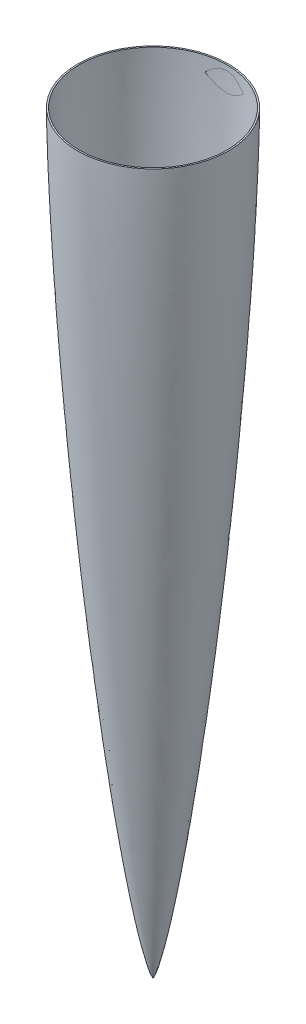
SolidWorks part; units mm, degrees
ref_plane "Front Plane" through (0, 0, 0) normal (1, 0, 0) x (0, 1, 0)
ref_plane "Top Plane" through (0, 0, 0) normal (0, 0, 1) x (0, 1, 0)
ref_plane "Right Plane" through (0, 0, 0) normal (0, 1, 0) x (-1, 0, 0)
sketch "Sketch2" plane through (0, 0, 0) normal (1, 0, 0) x (0, 1, 0)
  line L0 (0, 0) -> (1524, 0)
  line L1 (1524, 0) -> (1524, 152.4)
  spline S0 degree 4 poles (0, 0) (0.0024, 0.0076) (0.008, 0.0224) (0.0228, 0.0502) (0.0602, 0.1013) (0.1177, 0.1662) (0.1973, 0.2429) (0.3166, 0.346) (0.4663, 0.4619) (0.6411, 0.5854) (0.8409, 0.7163) (1.0863, 0.8681) (1.3805, 1.0392) (1.7988, 1.268) (2.2428, 1.4943) (2.73, 1.7308) (3.3252, 2.0064) (3.9582, 2.287) (5.2484, 2.832) (7.7002, 3.7871) (12.4184, 5.4349) (21.4879, 8.2045) (34.2024, 11.5666) (49.9837, 15.3041) (77.2138, 21.1912) (111.5094, 27.7893) (153.1274, 35.0456) (202.0796, 42.8366) (248.6768, 49.7602) (306.9942, 57.9227) (377.0645, 67.0588) (458.9113, 76.9376) (552.5524, 87.3436) (646.2759, 96.9776) (740.0687, 105.9093) (833.9221, 114.1801) (927.8297, 121.8101) (1021.7871, 128.8013) (1115.791, 135.1367) (1198.0833, 140.0715) (1268.6466, 143.8211) (1327.4672, 146.5841) (1374.5344, 148.5535) (1414.7685, 150.0006) (1448.1647, 151.0109) (1474.7196, 151.6715) (1491.9662, 152.0244) (1506.7504, 152.259) (1516.6071, 152.3627) (1521.5357, 152.3956) (1524, 152.4) knots 0 0 0 0 0 0.000021 0.000041 0.000082 0.000164 0.000247 0.000329 0.000493 0.000658 0.000805 0.000951 0.001245 0.001545 0.002047 0.002251 0.002657 0.003255 0.003853 0.005902 0.009516 0.016281 0.028569 0.040181 0.051794 0.088907 0.119611 0.150314 0.181018 0.211721 0.273128 0.334535 0.395942 0.457348 0.518755 0.580162 0.641569 0.702976 0.764383 0.825789 0.856493 0.887196 0.9179 0.948603 0.961452 0.974302 0.987151 0.993575 1 1 1 1 1 construction
  spline S1 degree 4 poles (0, 0) (0.0024, 0.0076) (0.008, 0.0224) (0.0228, 0.0502) (0.0602, 0.1013) (0.1177, 0.1662) (0.1973, 0.2429) (0.3166, 0.346) (0.4663, 0.4619) (0.6411, 0.5854) (0.8409, 0.7163) (1.0863, 0.8681) (1.3805, 1.0392) (1.7988, 1.268) (2.2428, 1.4943) (2.73, 1.7308) (3.3252, 2.0064) (3.9582, 2.287) (5.2484, 2.832) (7.7002, 3.7871) (12.4184, 5.4349) (21.4879, 8.2045) (34.2024, 11.5666) (49.9837, 15.3041) (77.2138, 21.1912) (111.5094, 27.7893) (153.1274, 35.0456) (202.0796, 42.8366) (248.6768, 49.7602) (306.9942, 57.9227) (377.0645, 67.0588) (458.9113, 76.9376) (552.5524, 87.3436) (646.2759, 96.9776) (740.0687, 105.9093) (833.9221, 114.1801) (927.8297, 121.8101) (1021.7871, 128.8013) (1115.791, 135.1367) (1198.0833, 140.0715) (1268.6466, 143.8211) (1327.4672, 146.5841) (1374.5344, 148.5535) (1414.7685, 150.0006) (1448.1647, 151.0109) (1474.7196, 151.6715) (1491.9662, 152.0244) (1506.7504, 152.259) (1516.6071, 152.3627) (1521.5357, 152.3956) (1524, 152.4) knots 0 0 0 0 0 0.000021 0.000041 0.000082 0.000164 0.000247 0.000329 0.000493 0.000658 0.000805 0.000951 0.001245 0.001545 0.002047 0.002251 0.002657 0.003255 0.003853 0.005902 0.009516 0.016281 0.028569 0.040181 0.051794 0.088907 0.119611 0.150314 0.181018 0.211721 0.273128 0.334535 0.395942 0.457348 0.518755 0.580162 0.641569 0.702976 0.764383 0.825789 0.856493 0.887196 0.9179 0.948603 0.961452 0.974302 0.987151 0.993575 1 1 1 1 1
  dimension "D1" = 1524
revolve "Revolve1" add sketch "Sketch2" angle 360 about L0
shell "Shell1" thickness 3 removed face at (0, 1524, -152.4)
equation "\"length\"= 25.4 * 12 * 5"
equation "\"diameter\" = 25.4 * 12"
equation "\"radius\"= \"diameter\" / 2"
equation "\"D1@Sketch2\"=\"length\""
